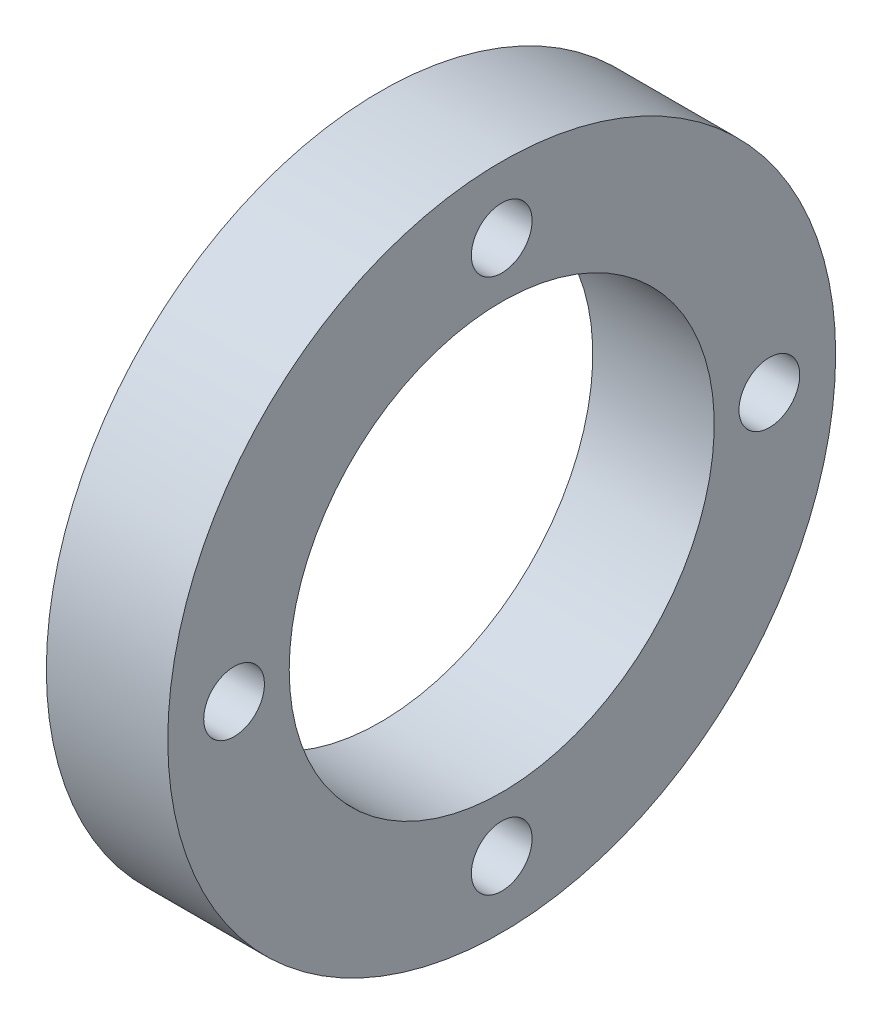
SolidWorks part; units mm, degrees
material "AISI Type A2 Tool Steel"
ref_plane "Front Plane" through (0, 0, 0) normal (0, 0, 1) x (1, 0, 0)
ref_plane "Top Plane" through (0, 0, 0) normal (0, 1, 0) x (1, 0, 0)
ref_plane "Right Plane" through (0, 0, 0) normal (1, 0, 0) x (0, 0, -1)
sketch "Top Layout" plane through (0, 0, 0) normal (0, 1, 0) x (1, 0, 0)
  line L0 (-114.046, -123.825) -> (-104.775, -123.825) construction
  line L1 (-104.775, -142.875) -> (-101.6, -142.875)
  line L2 (-104.775, -142.875) -> (-104.775, -104.775)
  line L3 (-104.775, -104.775) -> (-101.6, -104.775)
  line L4 (-101.6, -142.875) -> (-101.6, -104.775)
  line L5 (-104.775, -142.875) -> (-101.6, -104.775) construction
  line L6 (-104.775, -104.775) -> (-101.6, -142.875) construction
  line L7 (-19.05, -105.8164) -> (-101.6, -105.8164)
  line L8 (-19.05, -105.8164) -> (-19.05, -141.8336)
  line L9 (-19.05, -141.8336) -> (-101.6, -141.8336)
  line L10 (-101.6, -105.8164) -> (-101.6, -141.8336)
  line L11 (-19.05, -105.8164) -> (-101.6, -141.8336) construction
  line L12 (-19.05, -141.8336) -> (-101.6, -105.8164) construction
  line L13 (-133.096, -85.725) -> (-114.046, -85.725)
  line L14 (-133.096, -85.725) -> (-133.096, -161.925)
  line L15 (-133.096, -161.925) -> (-114.046, -161.925)
  line L16 (-114.046, -85.725) -> (-114.046, -161.925)
  line L17 (-133.096, -85.725) -> (-114.046, -161.925) construction
  line L18 (-133.096, -161.925) -> (-114.046, -85.725) construction
  line L19 (-104.775, -123.825) -> (0, -123.825) construction
  line L20 (0, -123.825) -> (0, 0) construction
  line L21 (-52.3528, -40.1717) -> (0, 0) construction
  line L22 (-70.6449, -16.3328) -> (-18.2922, 23.8388)
  line L23 (-34.0606, -64.0105) -> (18.2922, -23.8388)
  line L24 (-30.9251, 40.3023) -> (-122.2248, -29.7544)
  line L25 (-153.9748, -53.975) -> (-153.9748, -123.825)
  line L26 (-109.5248, -162.052) -> (109.5248, -162.052)
  line L27 (0, -162.052) -> (0, -123.825) construction
  line L28 (-109.5248, -162.052) -> (-109.5248, -20.0093) construction
  line L29 (-104.775, -142.875) -> (-104.775, -152.527)
  line L30 (-104.775, -152.527) -> (104.775, -152.527)
  line L31 (104.775, -104.775) -> (101.6, -104.775)
  line L32 (-144.4498, -73.025) -> (-109.5248, -73.025)
  line L33 (-144.4498, -73.025) -> (-144.4498, -123.825)
  line L34 (-144.4498, -123.825) -> (-109.5248, -123.825) construction
  line L35 (-109.5248, -73.025) -> (-109.5248, -162.052)
  line L36 (-144.4498, -73.025) -> (-109.5248, -123.825) construction
  line L37 (-144.4498, -123.825) -> (-109.5248, -73.025) construction
  line L38 (101.6, -142.875) -> (101.6, -104.775)
  line L39 (104.775, -142.875) -> (101.6, -142.875)
  line L40 (104.775, -142.875) -> (104.775, -104.775)
  line L41 (104.775, -142.875) -> (104.775, -152.527)
  line L42 (109.5248, -162.052) -> (109.5248, -20.0093) construction
  line L43 (30.9251, 40.3023) -> (122.2248, -29.7544)
  line L45 (19.05, -141.8336) -> (101.6, -141.8336)
  line L46 (101.6, -105.8164) -> (101.6, -141.8336)
  line L47 (19.05, -105.8164) -> (101.6, -105.8164)
  line L48 (19.05, -105.8164) -> (19.05, -141.8336)
  line L49 (133.096, -161.925) -> (114.046, -161.925)
  line L50 (114.046, -85.725) -> (114.046, -161.925)
  line L51 (133.096, -85.725) -> (114.046, -85.725)
  line L52 (133.096, -85.725) -> (133.096, -161.925)
  line L53 (144.4498, -123.825) -> (109.5248, -123.825) construction
  line L54 (109.5248, -73.025) -> (109.5248, -162.052)
  line L55 (144.4498, -73.025) -> (109.5248, -73.025)
  line L56 (144.4498, -73.025) -> (144.4498, -123.825)
  line L57 (-109.5248, -123.825) -> (-109.5248, -162.052) construction
  line L62 (-153.9748, -53.975) -> (-122.2248, -53.975)
  line L63 (-122.2248, -53.975) -> (-122.2248, -29.7544)
  line L64 (-144.4498, -123.825) -> (-153.9748, -123.825)
  line L65 (153.9748, -53.975) -> (153.9748, -123.825)
  line L66 (109.5248, -123.825) -> (109.5248, -162.052) construction
  line L67 (144.4498, -123.825) -> (153.9748, -123.825)
  line L68 (122.2248, -29.7544) -> (122.2248, -53.975)
  line L73 (-104.775, -104.775) -> (-104.775, -16.3647) construction
  line L74 (-95.25, -162.052) -> (-95.25, -9.0559) construction
  line L75 (-109.5248, -162.052) -> (-109.5248, -123.825) construction
  line L76 (109.5248, -162.052) -> (109.5248, -123.825) construction
  line L77 (122.2248, -53.975) -> (153.9748, -53.975)
  line L83 (104.775, -155.5496) -> (-104.775, -155.5496) construction
  line L88 (95.25, -162.052) -> (95.25, -9.0559) construction
  line L89 (104.775, -104.775) -> (104.775, -16.3647) construction
  line L92 (-104.775, -152.527) -> (-104.775, -162.052) construction
  line L93 (-14.605, -76.327) -> (14.605, -76.327)
  line L94 (-14.605, -76.327) -> (-14.605, -152.527)
  line L95 (-14.605, -152.527) -> (14.605, -152.527)
  line L96 (14.605, -76.327) -> (14.605, -152.527)
  line L97 (-14.605, -76.327) -> (14.605, -152.527) construction
  line L98 (-14.605, -152.527) -> (14.605, -76.327) construction
  line L99 (104.775, -152.527) -> (104.775, -162.052) construction
  line L100 (-19.05, -105.8164) -> (0, -105.8164) construction
  line L107 (0, -105.8164) -> (19.05, -105.8164) construction
  line L108 (104.775, -123.825) -> (114.046, -123.825) construction
  circle A0 centre (0, 0) radius 114.3
  circle A1 centre (0, 0) radius 6.35
  circle A2 centre (-52.3528, -40.1717) radius 17.8
  circle A3 centre (0, 0) radius 30.0482
  circle A4 centre (-52.3528, -40.1717) radius 30.0482
  arc A5 (-30.9251, 40.3023) -> (30.9251, 40.3023) centre (0, 0) cw
  point P2 (-103.1875, -123.825)
  point P7 (-60.325, -123.825)
  point P12 (-123.571, -123.825)
  point P30 (-126.9873, -98.425)
  point P35 (0, -114.427)
  point P53 (0, -152.527)
  dimension "D1" = 35.6
  dimension "D2" = 12.7
  dimension "D3" = 228.6
  dimension "D11" = 60.0964
  dimension "D12" = 50.8
  dimension "D14" = 52.5
  dimension "D4" = 3.175
  dimension "D5" = 19.05
  dimension "D6" = 76.2
  dimension "D7" = 82.55
  dimension "D8" = 38.1
  dimension "D9" = 104.775
  dimension "D10" = 18.0086
  dimension "D13" = 9.525
  dimension "D15" = 4.7498
  dimension "D16" = 9.525
  dimension "D17" = 9.652
  dimension "D18" = 50.8
  dimension "D19" = 12.446
  dimension "D20" = 65.9892
  dimension "D21" = 19.05
  dimension "D22" = 34.925
  dimension "D23" = 123.825
  dimension "D24" = 12.7
  dimension "D25" = 9.525
  dimension "D26" = 29.21
  dimension "D27" = 76.2
  dimension "D28" = 3.0226
sketch "Side Layout" plane through (0, 0, 0) normal (1, 0, 0) x (0, 0, -1)
  line L0 (0, -38.1) -> (0, 33.7344) construction
  line L1 (-114.3, -20.955) -> (114.3, -20.955)
  line L2 (-114.3, -20.955) -> (-114.3, -33.655)
  line L3 (-114.3, -33.655) -> (114.3, -33.655)
  line L4 (114.3, -20.955) -> (114.3, -33.655)
  line L5 (-114.3, -20.955) -> (114.3, -33.655) construction
  line L6 (-114.3, -33.655) -> (114.3, -20.955) construction
  line L7 (-9.525, -32.9406) -> (9.525, -32.9406)
  line L8 (-9.525, -32.9406) -> (-9.525, -38.1)
  line L9 (-9.525, -38.1) -> (9.525, -38.1)
  line L10 (9.525, -32.9406) -> (9.525, -38.1)
  line L11 (-9.525, -32.9406) -> (9.525, -38.1) construction
  line L12 (-9.525, -38.1) -> (9.525, -32.9406) construction
  line L13 (-11.9126, -29.3338) -> (11.9126, -29.3338)
  line L14 (-11.9126, -29.3338) -> (-11.9126, -32.9406)
  line L15 (-11.9126, -32.9406) -> (11.9126, -32.9406)
  line L16 (11.9126, -29.3338) -> (11.9126, -32.9406)
  line L17 (-11.9126, -29.3338) -> (11.9126, -32.9406) construction
  line L18 (-11.9126, -32.9406) -> (11.9126, -29.3338) construction
  line L19 (-6.35, -32.9406) -> (6.35, -32.9406)
  line L20 (-6.35, -32.9406) -> (-6.35, 33.7344)
  line L21 (-6.35, 33.7344) -> (6.35, 33.7344)
  line L22 (6.35, -32.9406) -> (6.35, 33.7344)
  line L23 (-6.35, -32.9406) -> (6.35, 33.7344) construction
  line L24 (-6.35, 33.7344) -> (6.35, -32.9406) construction
  line L25 (-162.052, 0) -> (-123.825, 0) construction
  line L26 (114.3, -33.655) -> (114.3, 0) construction
  line L27 (-142.875, 19.05) -> (-104.775, 19.05)
  line L28 (-40.1717, -9.525) -> (-40.1717, 5.4) construction
  line L29 (-142.875, 19.05) -> (-142.875, -19.05)
  line L30 (-142.875, -19.05) -> (-104.775, -19.05)
  line L31 (-104.775, 19.05) -> (-104.775, -19.05)
  line L32 (-142.875, 19.05) -> (-104.775, -19.05) construction
  line L33 (-142.875, -19.05) -> (-104.775, 19.05) construction
  line L34 (-130.175, -38.1) -> (-117.9516, -38.1) construction
  line L35 (-57.9717, -14.6) -> (-22.3717, -14.6)
  line L36 (-30.0482, -2.794) -> (30.0482, -2.794)
  line L37 (-30.0482, -2.794) -> (-30.0482, -20.955)
  line L38 (-30.0482, -20.955) -> (30.0482, -20.955)
  line L39 (30.0482, -2.794) -> (30.0482, -20.955)
  line L40 (-30.0482, -2.794) -> (30.0482, -20.955) construction
  line L41 (-30.0482, -20.955) -> (30.0482, -2.794) construction
  line L42 (-30.0482, -2.794) -> (-30.0482, 0) construction
  line L43 (-123.825, 0) -> (0, 0) construction
  line L44 (-57.9717, -14.6) -> (-57.9717, 25.4)
  line L45 (-57.9717, 25.4) -> (-22.3717, 25.4)
  line L46 (-22.3717, -14.6) -> (-22.3717, 25.4)
  line L47 (-19.05, 0) -> (19.05, 0)
  line L48 (-19.05, 0) -> (-19.05, -1.9812)
  line L49 (-19.05, -1.9812) -> (19.05, -1.9812)
  line L50 (19.05, 0) -> (19.05, -1.9812)
  line L51 (-19.05, 0) -> (19.05, -1.9812) construction
  line L52 (-19.05, -1.9812) -> (19.05, 0) construction
  line L53 (-70.2199, -3.175) -> (-10.1235, -3.175)
  line L54 (-70.2199, -3.175) -> (-70.2199, -15.875)
  line L55 (-70.2199, -15.875) -> (-10.1235, -15.875)
  line L56 (-10.1235, -3.175) -> (-10.1235, -15.875)
  line L57 (-70.2199, -3.175) -> (-10.1235, -15.875) construction
  line L58 (-70.2199, -15.875) -> (-10.1235, -3.175) construction
  line L59 (-40.1717, -9.525) -> (-40.1717, 0) construction
  line L60 (-57.9717, -14.6) -> (-22.3717, 25.4) construction
  line L61 (-57.9717, 25.4) -> (-22.3717, -14.6) construction
  line L62 (-22.3717, 0) -> (-57.9717, 0) construction
  line L63 (-137.8162, 0) -> (-123.825, -13.9912) construction
  line L64 (-139.065, 15.24) -> (-108.585, 15.24) construction
  line L65 (-139.065, 15.24) -> (-139.065, -15.24) construction
  line L66 (-139.065, -15.24) -> (-108.585, -15.24) construction
  line L67 (-108.585, 15.24) -> (-108.585, -15.24) construction
  line L68 (-139.065, 15.24) -> (-108.585, -15.24) construction
  line L69 (-139.065, -15.24) -> (-108.585, 15.24) construction
  line L70 (-137.8162, 0) -> (-123.825, 13.9912) construction
  line L71 (-123.825, -13.9912) -> (-109.8338, 0) construction
  line L72 (-123.825, 13.9912) -> (-109.8338, 0) construction
  line L73 (-137.8162, 0) -> (-109.8338, 0) construction
  line L74 (-123.825, -13.9912) -> (-123.825, 13.9912) construction
  line L75 (-6.35, 17.8594) -> (6.35, 17.8594)
  line L76 (114.3, 0) -> (-114.3, 0) construction
  line L77 (-22.3717, 19.05) -> (-6.35, 19.05) construction
  line L78 (-123.825, 38.1) -> (-97.9206, 38.1) construction
  line L79 (-19.05, -3.5814) -> (19.05, -3.5814)
  line L80 (-19.05, -3.5814) -> (-19.05, -1.9812)
  line L81 (-19.05, -1.9812) -> (19.05, -1.9812)
  line L82 (19.05, -3.5814) -> (19.05, -1.9812)
  line L83 (-19.05, -3.5814) -> (19.05, -1.9812) construction
  line L84 (-19.05, -1.9812) -> (19.05, -3.5814) construction
  line L85 (-8.7376, -16.7608) -> (8.7376, -16.7608)
  line L86 (-8.7376, -16.7608) -> (-8.7376, -29.3338)
  line L87 (-8.7376, -29.3338) -> (8.7376, -29.3338)
  line L88 (8.7376, -16.7608) -> (8.7376, -29.3338)
  line L89 (-8.7376, -16.7608) -> (8.7376, -29.3338) construction
  line L90 (-8.7376, -29.3338) -> (8.7376, -16.7608) construction
  line L91 (-8.7376, -3.5814) -> (8.7376, -3.5814)
  line L92 (-8.7376, -3.5814) -> (-8.7376, -16.1544)
  line L93 (-8.7376, -16.1544) -> (8.7376, -16.1544)
  line L94 (8.7376, -3.5814) -> (8.7376, -16.1544)
  line L95 (-8.7376, -3.5814) -> (8.7376, -16.1544) construction
  line L96 (-8.7376, -16.1544) -> (8.7376, -3.5814) construction
  circle A0 centre (-123.825, 0) radius 18.0086
  circle A1 centre (-123.825, 0) radius 38.1
  circle A2 centre (-139.065, 15.24) radius 1.905
  circle A3 centre (-108.585, 15.24) radius 1.905
  circle A4 centre (-108.585, -15.24) radius 1.905
  circle A5 centre (-139.065, -15.24) radius 1.905
  circle A6 centre (-137.8162, 0) radius 1.6002
  circle A7 centre (-123.825, 13.9912) radius 1.6002
  circle A8 centre (-109.8338, 0) radius 1.6002
  circle A9 centre (-123.825, -13.9912) radius 1.6002
  point P0 (0, -27.305)
  point P6 (0, -31.1372)
  point P7 (0, -35.5203)
  point P21 (0, 0.3969)
  point P32 (0, -11.8745)
  point P43 (0, -0.9906)
  point P55 (-40.1717, -9.525)
  point P72 (-40.1717, 5.4)
  point P88 (0, -23.0473)
  point P93 (0, -2.7813)
  point P102 (0, -9.8679)
  dimension "D17" = 3.81
  dimension "D18" = 3.2004
  dimension "D1" = 12.7
  dimension "D2" = 5.1594
  dimension "D3" = 19.05
  dimension "D4" = 3.6068
  dimension "D5" = 23.8252
  dimension "D6" = 12.7
  dimension "D7" = 18.161
  dimension "D8" = 1.9812
  dimension "D9" = 12.7
  dimension "D10" = 40
  dimension "D11" = 25.4
  dimension "D12" = 50.8
  dimension "D13" = 41.275
  dimension "D14" = 30.48
  dimension "D15" = 4.445
  dimension "D16" = 19.7866
  dimension "D19" = 15.875
  dimension "D20" = 6.35
  dimension "D21" = 38.1
  dimension "D22" = 1.6002
  dimension "D23" = 38.1
  dimension "D24" = 17.4752
  dimension "D25" = 12.573
ref_plane "Plane1" through (0, 25.4, 0) normal (0, 1, 0) x (1, 0, 0)
sketch "Sketch3" plane through (0, 25.4, 0) normal (0, 1, 0) x (1, 0, 0)
  line L0 (-104.775, -36.3747) -> (-30.9251, 20.2924)
  line L1 (-104.775, -104.775) -> (-104.775, -16.3647) construction
  line L2 (0, -200130.175) -> (0, 199882.0484) construction
  line L3 (-30.9251, 40.3023) -> (-122.2248, -29.7544) construction
  line L5 (-104.775, -36.3747) -> (-104.775, -77.6497)
  line L6 (-92.075, -77.6497) -> (-104.775, -77.6497)
  line L7 (30.9251, 20.2924) -> (104.775, -36.3747)
  line L8 (104.775, -77.6497) -> (92.075, -77.6497)
  line L9 (104.775, -36.3747) -> (104.775, -77.6497)
  line L11 (104.775, -104.775) -> (104.775, -16.3647) construction
  line L12 (30.9251, 40.3023) -> (122.2248, -29.7544) construction
  line L13 (92.075, -74.6536) -> (24.1423, -22.5271)
  line L14 (-32.2514, -66.3682) -> (20.1013, -26.1965)
  line L15 (-30.9251, 20.2924) -> (0, 44.022)
  line L16 (0, 44.022) -> (30.9251, 20.2924)
  line L17 (-92.075, -77.6497) -> (-92.075, -73.1917)
  line L19 (-92.075, -73.1917) -> (-52.3528, -73.1917)
  line L20 (92.075, -74.6536) -> (92.075, -77.6497)
  circle A0 centre (-52.3528, -40.1717) radius 17.8 construction
  circle A1 centre (-52.3528, -40.1717) radius 17.8
  circle A2 centre (0, 0) radius 6.35
  circle A3 centre (0, 0) radius 6.35 construction
  arc A4 (-52.3528, -73.1917) -> (-32.2514, -66.3682) centre (-52.3528, -40.1717) ccw
  arc A5 (20.1013, -26.1965) -> (24.1423, -22.5271) centre (0, 0) ccw
  arc A6 (30.9251, 20.2924) -> (-30.9251, 20.2924) centre (0, -20.01) ccw construction
  point P28 (0, 44.022)
  dimension "D1" = 33.02
  dimension "D5" = 50.8
  dimension "D2" = 41.275
  dimension "D3" = 34.925
  dimension "D4" = 12.7
  dimension "D6" = 38.1
ref_plane "Plane3" through (-104.775, 0, 0) normal (-1, 0, 0) x (0, 0, 1)
sketch "Sketch6" plane through (-104.775, 0, 0) normal (-1, 0, 0) x (0, 0, 1)
  line L0 (162.052, -25.4) -> (162.052, 25.4)
  line L1 (162.052, 25.4) -> (77.6497, 25.4)
  line L2 (36.3747, 25.4) -> (77.6497, 25.4) construction
  line L3 (147.7645, 11.1125) -> (162.052, 11.1125) construction
  line L4 (162.052, 0) -> (71.2997, 0) construction
  line L5 (77.6497, 25.4) -> (77.6497, 19.05)
  line L6 (77.6497, 19.05) -> (36.3747, 19.05)
  line L7 (36.3747, 19.05) -> (36.3747, 6.35)
  line L8 (36.3747, 6.35) -> (71.2997, 6.35)
  line L10 (99.6315, -3.175) -> (99.6315, 11.1125) construction
  line L11 (71.2997, -25.4) -> (162.052, -25.4)
  line L13 (71.2997, 6.35) -> (71.2997, -25.4)
  line L14 (152.527, -25.4) -> (152.527, 25.4) construction
  line L15 (99.6315, 11.1125) -> (99.6315, 25.4) construction
  line L16 (147.7645, 11.1125) -> (147.7645, 25.4) construction
  line L17 (94.869, -7.9375) -> (104.394, -7.9375) construction
  line L18 (94.869, -7.9375) -> (94.869, 25.4) construction
  line L19 (94.869, 25.4) -> (104.394, 25.4) construction
  line L20 (104.394, -7.9375) -> (104.394, 25.4) construction
  line L21 (94.869, -7.9375) -> (104.394, 25.4) construction
  line L22 (94.869, 25.4) -> (104.394, -7.9375) construction
  line L23 (147.7645, 11.1125) -> (147.7645, -3.175) construction
  line L24 (104.394, -7.9375) -> (123.825, -7.9375) construction
  line L25 (143.002, -7.9375) -> (152.527, -7.9375) construction
  line L26 (143.002, -7.9375) -> (143.002, 25.4) construction
  line L27 (143.002, 25.4) -> (152.527, 25.4) construction
  line L28 (152.527, -7.9375) -> (152.527, 25.4) construction
  line L29 (143.002, -7.9375) -> (152.527, 25.4) construction
  line L30 (143.002, 25.4) -> (152.527, -7.9375) construction
  line L31 (123.825, -7.9375) -> (152.527, -7.9375) construction
  line L32 (104.775, 19.05) -> (104.775, -19.05) construction
  line L34 (155.702, -25.4) -> (155.702, 25.4) construction
  circle A0 centre (109.8338, 0) radius 1.6002 construction
  circle A1 centre (123.825, 13.9912) radius 1.6002 construction
  circle A2 centre (137.8162, 0) radius 1.6002 construction
  circle A3 centre (123.825, -13.9912) radius 1.6002 construction
  circle A4 centre (109.8338, 0) radius 1.6002 construction
  circle A5 centre (123.825, 13.9912) radius 1.6002 construction
  circle A6 centre (137.8162, 0) radius 1.6002 construction
  circle A7 centre (123.825, -13.9912) radius 1.6002 construction
  circle A8 centre (123.825, 0) radius 18.0086 construction
  circle A9 centre (123.825, 0) radius 18.0086 construction
  circle A10 centre (123.825, 0) radius 9.525
  circle A11 centre (108.585, -15.24) radius 1.905 construction
  circle A12 centre (108.585, 15.24) radius 1.905 construction
  circle A13 centre (139.065, 15.24) radius 1.905 construction
  circle A14 centre (139.065, -15.24) radius 1.905 construction
  circle A15 centre (108.585, -15.24) radius 1.905
  circle A16 centre (108.585, 15.24) radius 1.905
  circle A17 centre (139.065, 15.24) radius 1.905
  circle A18 centre (139.065, -15.24) radius 1.905
  circle A19 centre (147.7645, 11.1125) radius 2.5527
  circle A26 centre (99.6315, 11.1125) radius 2.5527
  circle A27 centre (99.6315, -3.175) radius 2.5527
  circle A28 centre (147.7645, -3.175) radius 2.5527
  point P29 (0, 0)
  point P55 (99.6315, 8.7312)
  point P61 (147.7645, 8.7312)
  dimension "D4" = 19.05
  dimension "D7" = 5.1054
  dimension "D1" = 6.35
  dimension "D2" = 12.7
  dimension "D3" = 25.4
  dimension "D5" = 6.35
  dimension "D6" = 3.175
  dimension "D8" = 0.381
  dimension "D9" = 14.2875
  dimension "D10" = 9.525
  dimension "D12" = 33.3375
extrude "Side Plate Extrude" add sketch "Sketch6" along normal up to vertex (4.7498 mm away) up to point (-109.5248, 0, 73.025)
sketch "Sketch12" [suppressed] plane through (0, 19.05, 0) normal (0, 1, 0) x (1, 0, 0)
  line L0 (-104.775, -77.6497) -> (-104.775, -36.3747)
  line L1 (-104.775, -36.3747) -> (-92.075, -36.3747)
  line L3 (-92.075, -36.3747) -> (-92.075, -77.6497)
  line L5 (-92.075, -77.6497) -> (-104.775, -77.6497)
  line L6 (-98.425, -77.6497) -> (-98.425, -63.3622) construction
  line L7 (-98.425, -63.3622) -> (-98.425, -50.6622) construction
  line L8 (-98.425, -50.6622) -> (-98.425, -36.3747) construction
  line L10 (-98.425, -36.3747) -> (-104.775, -36.3747) construction
  circle A0 centre (-98.425, -63.3622) radius 2.5527
  circle A1 centre (-98.425, -50.6622) radius 2.5527
  dimension "D2" = 5.1054
  dimension "D1" = 12.7
  dimension "D3" = 12.7
sketch "Sketch15" plane through (-109.5248, 0, 0) normal (-1, 0, 0) x (0, 0, 1)
  line L0 (36.3747, 12.7) -> (44.3122, 12.7) construction
  line L1 (36.3747, 19.05) -> (36.3747, 6.35) construction
  line L2 (44.3122, 12.7) -> (57.0122, 12.7) construction
  line L3 (57.0122, 12.7) -> (69.7122, 12.7) construction
  line L4 (69.7122, 12.7) -> (77.6497, 12.7) construction
  line L5 (77.6497, 12.7) -> (77.6497, 19.05) construction
  circle A0 centre (44.3122, 12.7) radius 2.5527
  circle A1 centre (57.0122, 12.7) radius 2.5527
  circle A2 centre (69.7122, 12.7) radius 2.5527
  dimension "D1" = 5.1054
  dimension "D2" = 12.7
extrude "Custom Nutstrip Holes" cut sketch "Sketch15" against normal through all
ref_plane "Plane5" through (0, 0, 152.527) normal (0, 0, 1) x (1, 0, 0)
sketch "Sketch41" plane through (0, 0, 152.527) normal (0, 0, 1) x (1, 0, 0)
  line L0 (-104.775, -7.9375) -> (-104.775, 25.4) construction
  line L1 (-104.775, -7.9375) -> (-104.775, 12.7)
  line L2 (-104.775, -7.9375) -> (104.775, -7.9375)
  line L3 (104.775, -7.9375) -> (104.775, 12.7)
  line L4 (104.775, 25.4) -> (-104.775, 25.4)
  line L5 (0, -7.9375) -> (0, 25.4) construction
  line L6 (-104.775, 3.9624) -> (-100.0125, 3.9624) construction
  line L7 (-100.0125, 3.9624) -> (-100.0125, 25.4) construction
  line L8 (104.775, 3.9624) -> (100.0125, 3.9624) construction
  line L9 (100.0125, 3.9624) -> (100.0125, 25.4) construction
  line L10 (19.05, 20.6375) -> (23.8252, 20.6375) construction
  line L11 (19.05, 15.875) -> (78.5876, 15.875) construction
  line L12 (19.05, 15.875) -> (19.05, 25.4) construction
  line L13 (19.05, 25.4) -> (78.5876, 25.4) construction
  line L14 (78.5876, 15.875) -> (78.5876, 25.4) construction
  line L15 (19.05, 15.875) -> (78.5876, 25.4) construction
  line L16 (19.05, 25.4) -> (78.5876, 15.875) construction
  line L17 (23.8252, 20.6375) -> (38.1127, 20.6375) construction
  line L18 (38.1127, 20.6375) -> (52.4002, 20.6375) construction
  line L19 (52.4002, 20.6375) -> (66.6877, 20.6375) construction
  line L20 (-104.775, 25.4) -> (-112.395, 25.4)
  line L21 (-112.395, 25.4) -> (-112.395, 3.175)
  line L22 (-112.395, 3.175) -> (-109.5248, 3.175)
  line L23 (-109.5248, 3.175) -> (-109.5248, 12.7)
  line L24 (-109.5248, 12.7) -> (-104.775, 12.7)
  line L25 (-104.775, 12.7) -> (-104.775, 25.4) construction
  line L26 (104.775, 25.4) -> (112.395, 25.4)
  line L27 (112.395, 25.4) -> (112.395, 3.175)
  line L28 (112.395, 3.175) -> (109.5248, 3.175)
  line L29 (109.5248, 3.175) -> (109.5248, 12.7)
  line L30 (109.5248, 12.7) -> (104.775, 12.7)
  line L31 (104.775, 12.7) -> (104.775, 25.4) construction
  line L32 (-100.0125, 3.9624) -> (-87.3125, 3.9624) construction
  line L33 (-63.5, -1.5875) -> (0, -1.5875) construction
  line L34 (0, -1.5875) -> (63.5, -1.5875) construction
  line L35 (63.5, -1.5875) -> (63.5, -7.9375) construction
  circle A0 centre (-100.0125, 3.9624) radius 2.5527
  circle A1 centre (100.0125, 3.9624) radius 2.5527
  circle A2 centre (23.8252, 20.6375) radius 2.5527
  circle A3 centre (38.1127, 20.6375) radius 2.5527
  circle A4 centre (52.4002, 20.6375) radius 2.5527
  circle A5 centre (66.6877, 20.6375) radius 2.5527
  circle A6 centre (-66.6877, 20.6375) radius 2.5527
  circle A7 centre (-52.4002, 20.6375) radius 2.5527
  circle A8 centre (-38.1127, 20.6375) radius 2.5527
  circle A9 centre (-23.8252, 20.6375) radius 2.5527
  circle A10 centre (-87.3125, 3.9624) radius 2.5527
  circle A11 centre (87.3125, 3.9624) radius 2.5527
  circle A12 centre (-63.5, -1.5875) radius 2.5527
  circle A13 centre (63.5, -1.5875) radius 2.5527
  point P14 (48.8188, 20.6375)
  dimension "D3" = 5.1054
  dimension "D7" = 5.1054
  dimension "D1" = 21.4376
  dimension "D2" = 4.7625
  dimension "D4" = 9.525
  dimension "D5" = 59.5376
  dimension "D6" = 4.7752
  dimension "D8" = 14.2875
  dimension "D9" = 7.62
  dimension "D10" = 4.7498
  dimension "D11" = 12.7
  dimension "D12" = 9.525
  dimension "D13" = 19.05
  dimension "D14" = 12.7
  dimension "D15" = 6.35
  dimension "D16" = 63.5
sketch "Sketch43" plane through (-109.5248, 0, 0) normal (-1, 0, 0) x (0, 0, 1)
  line L1 (152.527, 12.7) -> (155.702, 12.7)
  line L2 (152.527, 12.7) -> (152.527, 25.4)
  line L3 (152.527, 25.4) -> (155.702, 25.4)
  line L4 (155.702, 12.7) -> (155.702, 25.4)
  line L5 (152.527, 12.7) -> (155.702, 25.4) construction
  line L6 (152.527, 25.4) -> (155.702, 12.7) construction
  line L7 (162.052, 25.4) -> (77.6497, 25.4) construction
  point P4 (154.1145, 19.05)
  dimension "D1" = 3.175
extrude "Cut-Extrude19" cut sketch "Sketch43" against normal through all
sketch "Sketch44" plane through (0, 25.4, 0) normal (0, 1, 0) x (1, 0, 0)
  line L0 (73.8315, -147.7645) -> (73.8315, -152.527) construction
  line L1 (92.075, -74.6536) -> (92.075, -77.6497) construction
  line L2 (-92.075, -77.6497) -> (-92.075, -73.1917) construction
  line L3 (0, -123.825) -> (0, 0) construction
  line L4 (-92.075, -73.1917) -> (-52.3528, -73.1917) construction
  line L5 (-104.775, -104.775) -> (-104.775, -16.3647) construction
  line L6 (-32.2514, -66.3682) -> (20.1013, -26.1965) construction
  line L21 (-104.775, -68.1247) -> (-104.775, -152.527)
  line L22 (-104.775, -152.527) -> (104.775, -152.527)
  line L23 (104.775, -152.527) -> (104.775, -68.1247)
  line L34 (-104.775, -99.6315) -> (-100.0125, -99.6315) construction
  line L35 (-104.775, -147.7645) -> (-100.0125, -147.7645) construction
  line L36 (0, -152.527) -> (0, -35.6178) construction
  line L38 (30.969, -147.7645) -> (45.2565, -147.7645) construction
  line L39 (45.2565, -147.7645) -> (59.544, -147.7645) construction
  line L40 (59.544, -147.7645) -> (73.8315, -147.7645) construction
  line L41 (23.8252, -152.527) -> (30.969, -152.527) construction
  line L42 (104.775, -152.527) -> (-104.775, -152.527) construction
  line L43 (30.969, -152.527) -> (38.1127, -152.527) construction
  line L44 (30.969, -152.527) -> (30.969, -147.7645) construction
  line L45 (-92.075, -77.6497) -> (-104.775, -77.6497) construction
  line L48 (-35.1507, -62.5899) -> (-8.9743, -42.504) construction
  line L49 (-8.9743, -42.504) -> (17.2021, -22.4182) construction
  line L50 (45.5313, -32.9364) -> (87.3125, -64.9962) construction
  line L51 (92.075, -74.6536) -> (24.1423, -22.5271) construction
  line L52 (104.775, -77.6497) -> (92.075, -77.6497) construction
  line L79 (-104.775, -68.1247) -> (-92.075, -68.1247)
  line L80 (-92.075, -68.1247) -> (-92.075, -63.6667)
  line L85 (21.8118, -8.7328) -> (92.075, -62.6476)
  line L86 (-38.0499, -58.8115) -> (14.3028, -18.6398)
  line L87 (-92.075, -63.6667) -> (-52.3528, -63.6667)
  line L88 (92.075, -62.6476) -> (92.075, -68.1247)
  line L89 (92.075, -68.1247) -> (104.775, -68.1247)
  circle A0 centre (-73.8315, -147.7645) radius 2.5527
  circle A1 centre (-59.544, -147.7645) radius 2.5527
  circle A2 centre (-45.2565, -147.7645) radius 2.5527
  circle A3 centre (-30.969, -147.7645) radius 2.5527
  circle A17 centre (-100.0125, -99.6315) radius 2.5527
  circle A18 centre (-100.0125, -147.7645) radius 2.5527
  circle A19 centre (100.0125, -147.7645) radius 2.5527
  circle A20 centre (100.0125, -99.6315) radius 2.5527
  circle A21 centre (30.969, -147.7645) radius 2.5527
  circle A22 centre (45.2565, -147.7645) radius 2.5527
  circle A23 centre (59.544, -147.7645) radius 2.5527
  circle A24 centre (73.8315, -147.7645) radius 2.5527
  circle A25 centre (-87.3125, -68.4292) radius 4.7625 construction
  circle A26 centre (-35.1507, -62.5899) radius 4.7625 construction
  circle A27 centre (-8.9743, -42.504) radius 4.7625 construction
  circle A28 centre (17.2021, -22.4182) radius 4.7625 construction
  circle A29 centre (45.5313, -32.9364) radius 4.7625 construction
  circle A30 centre (87.3125, -64.9962) radius 4.7625 construction
  circle A32 centre (-87.3125, -68.4292) radius 2.5527
  circle A33 centre (-35.1507, -62.5899) radius 2.5527
  circle A34 centre (-8.9743, -42.504) radius 2.5527 construction
  circle A35 centre (17.2021, -22.4182) radius 2.5527
  circle A36 centre (45.5313, -32.9364) radius 2.5527
  circle A37 centre (87.3125, -64.9962) radius 2.5527
  circle A38 centre (-97.155, -85.2697) radius 7.62 construction
  circle A39 centre (97.155, -85.2697) radius 7.62 construction
  circle A40 centre (24.5121, -32.4156) radius 7.62 construction
  arc A41 (20.1013, -26.1965) -> (24.1423, -22.5271) centre (0, 0) ccw construction
  circle A42 centre (-97.155, -85.2697) radius 2.5527
  circle A43 centre (24.5121, -32.4156) radius 2.5527
  circle A44 centre (97.155, -85.2697) radius 2.5527
  arc A56 (14.3028, -18.6398) -> (21.8118, -8.7328) centre (0, 0) ccw
  arc A57 (-52.3528, -63.6667) -> (-38.0499, -58.8115) centre (-52.3528, -40.1717) ccw
  point P4 (-104.775, -152.527)
  dimension "D2" = 5.1054
  dimension "D7" = 5.1054
  dimension "D8" = 15.24
  dimension "D3" = 9.525
  dimension "D9" = 9.525
  dimension "D4" = 4.7625
  dimension "D5" = 14.2875
  dimension "D6" = 9.525
  dimension "D1" = 4.7625
  dimension "D10" = 52.664
sketch "Sketch72" plane through (0, 25.4, 0) normal (0, 1, 0) x (1, 0, 0)
  line L0 (-104.775, -68.1247) -> (-104.775, -152.527) construction
  line L1 (-104.775, -152.527) -> (-109.5248, -152.527)
  line L2 (-104.775, -152.527) -> (-104.775, -135.0645)
  line L3 (-104.775, -135.0645) -> (-109.5248, -135.0645)
  line L4 (-109.5248, -152.527) -> (-109.5248, -135.0645)
  line L5 (-104.775, -152.527) -> (-109.5248, -135.0645) construction
  line L6 (-104.775, -135.0645) -> (-109.5248, -152.527) construction
  line L7 (-104.775, -152.527) -> (104.775, -152.527) construction
  line L8 (-77.0065, -152.527) -> (-73.8315, -147.7645) construction
  line L9 (-77.0065, -152.527) -> (-27.794, -152.527)
  line L10 (-77.0065, -152.527) -> (-77.0065, -155.5496)
  line L11 (-77.0065, -155.5496) -> (-27.794, -155.5496)
  line L12 (-27.794, -152.527) -> (-27.794, -155.5496)
  line L13 (-77.0065, -152.527) -> (-27.794, -155.5496) construction
  line L14 (-77.0065, -155.5496) -> (-27.794, -152.527) construction
  line L15 (-27.794, -152.527) -> (-30.969, -147.7645) construction
  line L16 (-77.0065, -152.527) -> (-77.0065, -147.7645) construction
  line L18 (-104.775, -93.5247) -> (-109.5248, -93.5247)
  line L19 (-104.775, -93.5247) -> (-104.775, -112.3315)
  line L20 (-104.775, -112.3315) -> (-109.5248, -112.3315)
  line L21 (-109.5248, -93.5247) -> (-109.5248, -112.3315)
  line L22 (-104.775, -93.5247) -> (-109.5248, -112.3315) construction
  line L23 (-104.775, -112.3315) -> (-109.5248, -93.5247) construction
  line L24 (0, -152.527) -> (-12.7, -152.527)
  line L25 (0, -152.527) -> (0, -155.5496)
  line L26 (0, -155.5496) -> (-12.7, -155.5496)
  line L27 (-12.7, -152.527) -> (-12.7, -155.5496)
  line L28 (0, -152.527) -> (-12.7, -155.5496) construction
  line L29 (0, -155.5496) -> (-12.7, -152.527) construction
  line L30 (-104.775, -68.1247) -> (-109.5248, -68.1247)
  line L31 (-104.775, -68.1247) -> (-104.775, -77.6497)
  line L32 (-104.775, -77.6497) -> (-109.5248, -77.6497)
  line L33 (-109.5248, -68.1247) -> (-109.5248, -77.6497)
  line L34 (-104.775, -68.1247) -> (-109.5248, -77.6497) construction
  line L35 (-104.775, -77.6497) -> (-109.5248, -68.1247) construction
  line L38 (-103.505, -155.5496) -> (-90.805, -155.5496)
  line L39 (-90.805, -152.527) -> (-90.805, -155.5496)
  line L40 (-103.505, -155.5496) -> (-103.505, -152.527)
  line L41 (-103.505, -155.5496) -> (-90.805, -152.527) construction
  line L42 (-103.505, -152.527) -> (-90.805, -152.527)
  line L43 (-77.0065, -147.7645) -> (-73.8315, -147.7645) construction
  line L44 (-103.505, -152.527) -> (-101.5221, -149.823) construction
  circle A0 centre (-100.0125, -147.7645) radius 2.5527 construction
  circle A1 centre (-73.8315, -147.7645) radius 2.5527 construction
  circle A2 centre (-30.969, -147.7645) radius 2.5527 construction
  point P4 (-107.1499, -143.7958)
  point P5 (-100.0125, -147.7645)
  point P16 (-52.4002, -154.0383)
  point P18 (-97.155, -154.0383)
  point P25 (-107.1499, -102.9281)
  point P34 (-6.35, -154.0383)
  point P39 (-107.1499, -72.8872)
  dimension "D1" = 4.7498
  dimension "D2" = 12.7
  dimension "D3" = 12.7
  dimension "D4" = 12.7
  dimension "D5" = 9.525
  dimension "D6" = 15.875
  dimension "D7" = 12.7
  dimension "D8" = 3.175
  dimension "D9" = 1.27
  dimension "D10" = 3.0226
sketch "Sketch73" plane through (-109.5248, 0, 0) normal (-1, 0, 0) x (0, 0, 1)
  line L1 (77.6497, 25.4) -> (93.5247, 25.4)
  line L2 (77.6497, 25.4) -> (77.6497, 30.1625)
  line L3 (77.6497, 30.1625) -> (93.5247, 30.1625)
  line L4 (93.5247, 25.4) -> (93.5247, 30.1625)
  line L5 (77.6497, 25.4) -> (93.5247, 30.1625) construction
  line L6 (77.6497, 30.1625) -> (93.5247, 25.4) construction
  line L7 (112.3315, 25.4) -> (135.0645, 25.4)
  line L8 (112.3315, 25.4) -> (112.3315, 30.1625)
  line L9 (112.3315, 30.1625) -> (135.0645, 30.1625)
  line L10 (135.0645, 25.4) -> (135.0645, 30.1625)
  line L11 (112.3315, 25.4) -> (135.0645, 30.1625) construction
  line L12 (112.3315, 30.1625) -> (135.0645, 25.4) construction
  line L13 (155.702, 25.4) -> (162.052, 25.4)
  line L14 (155.702, 25.4) -> (155.702, 30.1625)
  line L15 (155.702, 30.1625) -> (162.052, 30.1625)
  line L16 (162.052, 25.4) -> (162.052, 30.1625)
  line L17 (155.702, 25.4) -> (162.052, 30.1625) construction
  line L18 (155.702, 30.1625) -> (162.052, 25.4) construction
  point P4 (85.5872, 27.7812)
  point P10 (123.698, 27.7812)
  point P16 (158.877, 27.7812)
  dimension "D1" = 4.7625
extrude "Boss-Extrude28" add sketch "Sketch73" against normal through all
sketch "Sketch108" plane through (-104.775, 0, 0) normal (1, 0, 0) x (0, 0, -1)
  line L0 (-93.5247, 30.1625) -> (-77.6497, 30.1625) construction
  line L1 (-77.6497, 19.05) -> (-68.1247, 19.05)
  line L2 (-77.6497, 19.05) -> (-77.6497, 30.1625)
  line L3 (-77.6497, 30.1625) -> (-68.1247, 30.1625)
  line L4 (-68.1247, 19.05) -> (-68.1247, 30.1625)
  line L5 (-77.6497, 19.05) -> (-68.1247, 30.1625) construction
  line L6 (-77.6497, 30.1625) -> (-68.1247, 19.05) construction
  circle A0 centre (-72.8872, 24.6062) radius 2.5527
  circle A1 centre (-69.7122, 12.7) radius 2.5527 construction
  point P4 (-72.8872, 24.6062)
  dimension "D1" = 9.525
extrude "Boss-Extrude35" add sketch "Sketch108" against normal through all
sketch "Sketch90" plane through (-104.775, 0, 0) normal (1, 0, 0) x (0, 0, -1)
  line L0 (-162.052, 30.1625) -> (-155.702, 30.1625) construction
  line L1 (-152.4508, 12.7) -> (-155.7782, 12.7)
  line L2 (-152.4508, 12.7) -> (-152.4508, 25.273)
  line L3 (-152.4508, 30.1625) -> (-155.7782, 30.1625)
  line L4 (-155.7782, 12.7) -> (-155.7782, 30.1625)
  line L5 (-152.4508, 12.7) -> (-155.7782, 30.1625) construction
  line L6 (-152.4508, 30.1625) -> (-155.7782, 12.7) construction
  line L7 (-152.527, 12.7) -> (-155.702, 12.7) construction
  line L8 (-53.8372, 6.477) -> (-53.8372, 6.35) construction
  line L9 (-36.3747, 6.35) -> (-71.2997, 6.35) construction
  line L10 (-135.0645, 30.1625) -> (-112.3315, 30.1625) construction
  line L11 (-152.4508, 30.1625) -> (-134.9883, 30.1625)
  line L12 (-152.4508, 30.1625) -> (-152.4508, 25.273) construction
  line L13 (-152.4508, 25.273) -> (-134.9883, 25.273)
  line L14 (-134.9883, 30.1625) -> (-134.9883, 25.273)
  line L15 (-152.4508, 30.1625) -> (-134.9883, 25.273) construction
  line L16 (-152.4508, 25.273) -> (-134.9883, 30.1625) construction
  line L17 (-112.4077, 30.1625) -> (-93.4485, 30.1625)
  line L18 (-112.4077, 30.1625) -> (-112.4077, 25.273)
  line L19 (-112.4077, 25.273) -> (-93.4485, 25.273)
  line L20 (-93.4485, 30.1625) -> (-93.4485, 25.273)
  line L21 (-112.4077, 30.1625) -> (-93.4485, 25.273) construction
  line L22 (-112.4077, 25.273) -> (-93.4485, 30.1625) construction
  line L23 (-36.3747, 19.05) -> (-36.3747, 6.35) construction
  line L24 (-68.1247, 19.05) -> (-36.3747, 19.05)
  line L25 (-68.1247, 19.05) -> (-68.1247, 18.923) construction
  line L26 (-68.1247, 18.923) -> (-36.3747, 18.923)
  line L27 (-36.3747, 19.05) -> (-36.3747, 18.923)
  line L28 (-68.1247, 19.05) -> (-36.3747, 18.923) construction
  line L29 (-68.1247, 18.923) -> (-36.3747, 19.05) construction
  line L30 (-152.4508, 25.273) -> (-152.4508, 30.1625) construction
  line L31 (-36.3747, 6.477) -> (-71.2997, 6.477)
  line L32 (-36.3747, 6.477) -> (-36.3747, -25.4)
  line L33 (-36.3747, -25.4) -> (-71.2997, -25.4)
  line L34 (-71.2997, 6.477) -> (-71.2997, -25.4)
  line L35 (-36.3747, 6.477) -> (-71.2997, -25.4) construction
  line L36 (-36.3747, -25.4) -> (-71.2997, 6.477) construction
  line L37 (-155.702, 21.4312) -> (-155.7782, 21.4312) construction
  line L38 (-155.702, 12.7) -> (-155.702, 30.1625) construction
  line L39 (-152.527, 19.05) -> (-152.4508, 19.05) construction
  line L40 (-152.527, 25.4) -> (-152.527, 12.7) construction
  line L41 (-143.7196, 25.273) -> (-143.7196, 25.4) construction
  line L42 (-152.527, 25.4) -> (-135.0645, 25.4) construction
  line L43 (-135.0645, 25.4) -> (-134.9883, 25.4) construction
  line L44 (-112.3315, 27.7812) -> (-112.4077, 27.7812) construction
  line L45 (-112.3315, 30.1625) -> (-112.3315, 25.4) construction
  line L46 (-102.9281, 25.4) -> (-102.9281, 25.273) construction
  line L47 (-112.3315, 25.4) -> (-93.5247, 25.4) construction
  line L48 (-93.5247, 25.4) -> (-93.4485, 25.4) construction
  line L49 (-71.2997, -25.4) -> (-162.052, -25.4) construction
  line L50 (-71.2997, 6.35) -> (-71.2997, -25.4) construction
  line L51 (-68.1247, 19.05) -> (-68.1247, 30.1625) construction
  line L52 (-93.5247, 30.1625) -> (-68.1247, 30.1625) construction
  line L53 (-68.2517, 30.1625) -> (-68.1247, 30.1625)
  line L54 (-68.2517, 30.1625) -> (-68.2517, 18.923)
  line L55 (-68.2517, 18.923) -> (-68.1247, 18.923)
  line L56 (-68.1247, 30.1625) -> (-68.1247, 19.05)
  line L57 (-68.2517, 30.1625) -> (-68.1247, 18.923) construction
  line L58 (-68.2517, 18.923) -> (-68.1247, 30.1625) construction
  line L59 (-68.1247, 19.05) -> (-68.1247, 18.923) construction
  point P4 (-154.1145, 21.4312)
  point P10 (-154.1145, 12.7)
  point P17 (-143.7196, 27.7177)
  point P22 (-102.9281, 27.7178)
  point P29 (-52.2497, 18.9865)
  point P37 (-53.8372, -9.4615)
  point P72 (-68.1882, 24.5427)
  dimension "D1" = 0.0762
  dimension "D2" = 0.127
extrude "Side Plate Tolerences" cut sketch "Sketch90" against normal through all
sketch "Sketch111" plane through (-109.5248, 0, 0) normal (-1, 0, 0) x (0, 0, 1)
  circle A0 centre (123.825, 0) radius 11.1125
  dimension "D1" = 22.225
extrude "Cut-Extrude21" cut sketch "Sketch111" against normal through all
sketch "Sketch113" plane through (-109.5248, 0, 0) normal (-1, 0, 0) x (0, 0, 1)
  line L0 (123.825, -13.9954) -> (123.825, 0) construction
  circle A0 centre (123.825, -13.9954) radius 1.5875
  dimension "D2" = 3.175
  dimension "D1" = 13.9954
extrude "Cut-Extrude23" cut sketch "Sketch113" against normal through all
pattern_circular "CirPattern1" count 4 over 360 about axis through (-104.775, 0, 123.825) along (-1, 0, 0) of "Cut-Extrude23"
chamfer "Chamfer8" distance 12.7 1 edges at (-107.1499, -25.4, 71.2997)
fillet "Fillet15" radius 2.54 3 edges at (-107.1499, -12.7, 71.2997) (-107.1499, -25.4, 83.9997) (-107.1499, -25.4, 162.052)
fillet "Fillet26" radius 1.27 7 edges at (-107.1499, 6.477, 36.3747) (-107.1499, 18.923, 36.3747) (-107.1499, 30.1625, 68.2517) (-107.1499, 25.273, 152.4508) (-107.1499, 30.1625, 155.7782) (-107.1499, 30.1625, 162.052) (-107.1499, 6.477, 71.2997)
fillet "Fillet29" radius 0.635 3 edges at (-107.1499, 30.1625, 93.4485) (-107.1499, 30.1625, 112.4077) (-107.1499, 30.1625, 134.9883)
sketch "Sketch109" plane through (-104.775, 0, 0) normal (1, 0, 0) x (0, 0, -1)
  line L0 (-85.0518, -25.4) -> (-159.512, -25.4) construction
  line L1 (-90.3497, -25.4) -> (-71.2997, -25.4)
  line L2 (-90.3497, -25.4) -> (-90.3497, -15.875)
  line L3 (-90.3497, -15.875) -> (-71.2997, -15.875)
  line L4 (-71.2997, -25.4) -> (-71.2997, -15.875)
  line L5 (-90.3497, -25.4) -> (-71.2997, -15.875) construction
  line L6 (-90.3497, -15.875) -> (-71.2997, -25.4) construction
  line L7 (-71.2997, 5.207) -> (-71.2997, -11.6479) construction
  point P4 (-80.8247, -20.6375)
  dimension "D1" = 9.525
  dimension "D2" = 19.05
extrude "Cut-Extrude20" cut sketch "Sketch109" against normal through all
fillet "Fillet30" radius 1.27 3 edges at (-107.1499, -25.4, 90.3497) (-107.1499, -15.875, 90.3497) (-107.1499, -15.875, 74.4747)
sketch "Sketch112" plane through (-109.5248, 0, 0) normal (1, 0, 0) x (0, 0, -1)
  circle A0 centre (-123.825, 0) radius 123.825
extrude "Cut-Extrude22" cut sketch "Sketch112" along normal offset from surface (1.5748 mm away) 3.175 up to face at (-104.775, 1.5875, 137.8204)
sketch "Sketch115" plane through (-107.95, 0, 0) normal (-1, 0, 0) x (0, 0, 1)
  circle A0 centre (109.8296, 0) radius 1.5875 construction
  circle A1 centre (123.825, 13.9954) radius 1.5875 construction
  circle A2 centre (137.8204, 0) radius 1.5875 construction
  circle A3 centre (123.825, -13.9954) radius 1.5875 construction
  circle A4 centre (123.825, 0) radius 11.1125 construction
  circle A5 centre (109.8296, 0) radius 1.5875
  circle A6 centre (123.825, 13.9954) radius 1.5875
  circle A7 centre (137.8204, 0) radius 1.5875
  circle A8 centre (123.825, -13.9954) radius 1.5875
  circle A9 centre (123.825, 0) radius 11.1125
  circle A10 centre (123.825, 0) radius 17.4625
  circle A11 centre (109.8296, 0) radius 2.75 construction
  dimension "D1" = 34.925
  dimension "D2" = 5.5
extrude "Boss-Extrude36" add sketch "Sketch115" along normal blind 6.35 separate body
delete or keep bodies "Body-Delete/Keep 1" type keep bodies bodies 269
delete or keep bodies "Body-Delete/Keep 2" [suppressed] type keep bodies bodies 266
